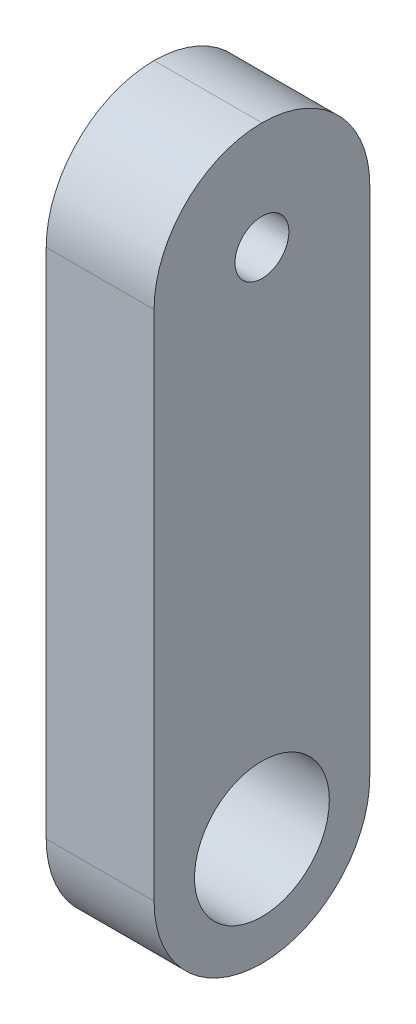
SolidWorks part; units mm, degrees
ref_plane "Front" through (0, 0, 0) normal (0, 0, 1) x (1, 0, 0)
ref_plane "Top" through (0, 0, 0) normal (0, 1, 0) x (1, 0, 0)
ref_plane "Right" through (0, 0, 0) normal (1, 0, 0) x (0, 0, -1)
sketch "Sketch1" plane through (0, 0, 0) normal (1, 0, 0) x (0, 0, -1)
  line L1 (0, 0) -> (8, 0)
  line L2 (0, 0) -> (0, -27)
  line L3 (0, -27) -> (8, -27)
  line L4 (8, 0) -> (8, -27)
  dimension "D1" = 27
  dimension "D2" = 8
extrude "Boss-Extrude1" add sketch "Sketch1" along normal blind 4
sketch "Sketch2" plane through (4, 0, 0) normal (1, 0, 0) x (0, 0, -1)
  line L0 (8, -27) -> (8, 0) construction
  line L1 (8, 0) -> (0, 0) construction
  line L2 (0, -27) -> (8, -27) construction
  circle A0 centre (4, -23) radius 2.5
  circle A1 centre (4, -4) radius 1
  dimension "D1" = 5
  dimension "D2" = 2
  dimension "D3" = 4
  dimension "D4" = 4
  dimension "D5" = 4
  dimension "D6" = 4
extrude "Cut-Extrude1" cut sketch "Sketch2" against normal through all
fillet "Fillet1" radius 4 4 edges at (2, -27, -8) (2, -27, 0) (2, 0, 0) (2, 0, -8)
equation "\"滑动-垂直孔\" = 0.6"
equation "\"滑动-水平孔\"= 0.3"
equation "\"松动-垂直孔\" = 0.3"
equation "\"松动-水平孔\"= 0.1"
equation "\"正常-垂直孔\" = 0.15"
equation "\"正常-水平孔\"= 0"
equation "\"紧缩-垂直孔\"= 0"
equation "\"紧缩-水平孔\"= - 0.1"
equation "\"D1@Sketch2\"=\"紧缩-垂直孔\"+5"
equation "\"D2@Sketch2\"=\"紧缩-垂直孔\"+2"
